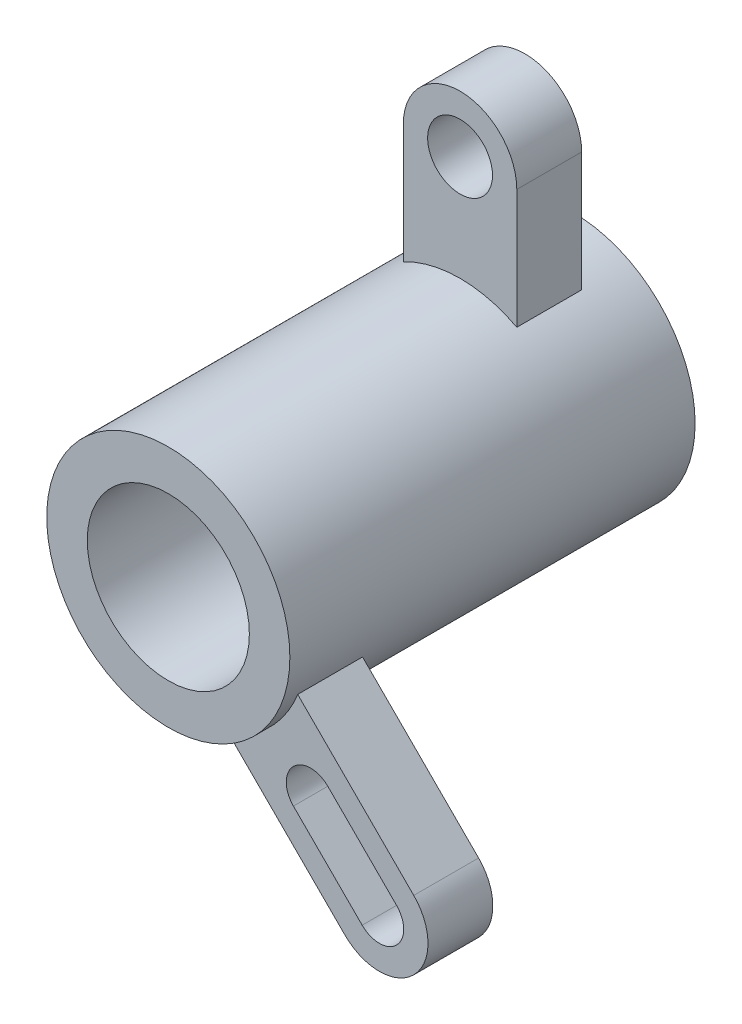
SolidWorks part; units mm, degrees
ref_plane "Спереди" through (0, 0, 0) normal (0, 0, 1) x (1, 0, 0)
ref_plane "Сверху" through (0, 0, 0) normal (0, 1, 0) x (1, 0, 0)
ref_plane "Справа" through (0, 0, 0) normal (1, 0, 0) x (0, 0, -1)
sketch "Эскиз1" plane through (0, 0, 0) normal (0, 0, 1) x (1, 0, 0)
  line L0 (0, 0) -> (0, 14) construction
  line L1 (-3.5, 0) -> (-3.5, 14)
  line L2 (3.5, 0) -> (3.5, 14)
  line L3 (0, 0) -> (12.0208, -12.0208) construction
  line L4 (2.1213, 2.1213) -> (14.1421, -9.8995)
  line L5 (-2.1213, -2.1213) -> (9.8995, -14.1421)
  line L6 (12.0208, -12.0208) -> (7.7782, -7.7782) construction
  line L7 (10.9602, -13.0815) -> (6.7175, -8.8388)
  line L8 (13.0815, -10.9602) -> (8.8388, -6.7175)
  circle A0 centre (0, 0) radius 5
  circle A1 centre (0, 0) radius 7.5
  arc A2 (-3.5, 0) -> (3.5, 0) centre (0, 0) ccw
  arc A3 (3.5, 14) -> (-3.5, 14) centre (0, 14) ccw
  circle A4 centre (0, 14) radius 2
  arc A5 (2.1213, 2.1213) -> (-2.1213, -2.1213) centre (0, 0) ccw
  arc A6 (9.8995, -14.1421) -> (14.1421, -9.8995) centre (12.0208, -12.0208) ccw
  arc A7 (10.9602, -13.0815) -> (13.0815, -10.9602) centre (12.0208, -12.0208) ccw
  arc A8 (8.8388, -6.7175) -> (6.7175, -8.8388) centre (7.7782, -7.7782) ccw
  point P5 (0, 7)
  point P13 (6.0104, -6.0104)
  point P21 (9.8995, -9.8995)
  dimension "D1" = 10
  dimension "D4" = 14
  dimension "D5" = 4
  dimension "D3" = 7
  dimension "D6" = 135
  dimension "D7" = 6
  dimension "D8" = 17
  dimension "D9" = 3
  dimension "D10" = 6
  dimension "D2" = 2.5
extrude "Бобышка-Вытянуть1" add sketch "Эскиз1" along normal blind 25 contours L5 A1 L4 A0 | L4 A1 L2 A0 | L1 A1 L5 A0 | L2 A1 L1 A0 region at (-4.6397, -2.2909, 0) region at (0, 5.8664, 0) region at (5.6194, 2.0317, 0) region at (4.2273, -4.2273, 0)
extrude "Бобышка-Вытянуть2" add sketch "Эскиз1<3>" along normal blind 4 from offset 3 contours L2 A3 L1 A1 A4 region at (0, 11.5507, 0)
sketch "Эскиз1<3>" plane through (0, 0, 0) normal (0, 0, 1) x (1, 0, 0) same geometry as "Эскиз1"
extrude "Бобышка-Вытянуть3" add sketch "Эскиз1<4>" along normal blind 4 from offset 20 contours L5 A6 L4 A1 A8 L8 A7 L7 region at (5.4261, -5.4261, 0)
sketch "Эскиз1<4>" plane through (0, 0, 0) normal (0, 0, 1) x (1, 0, 0) same geometry as "Эскиз1"
